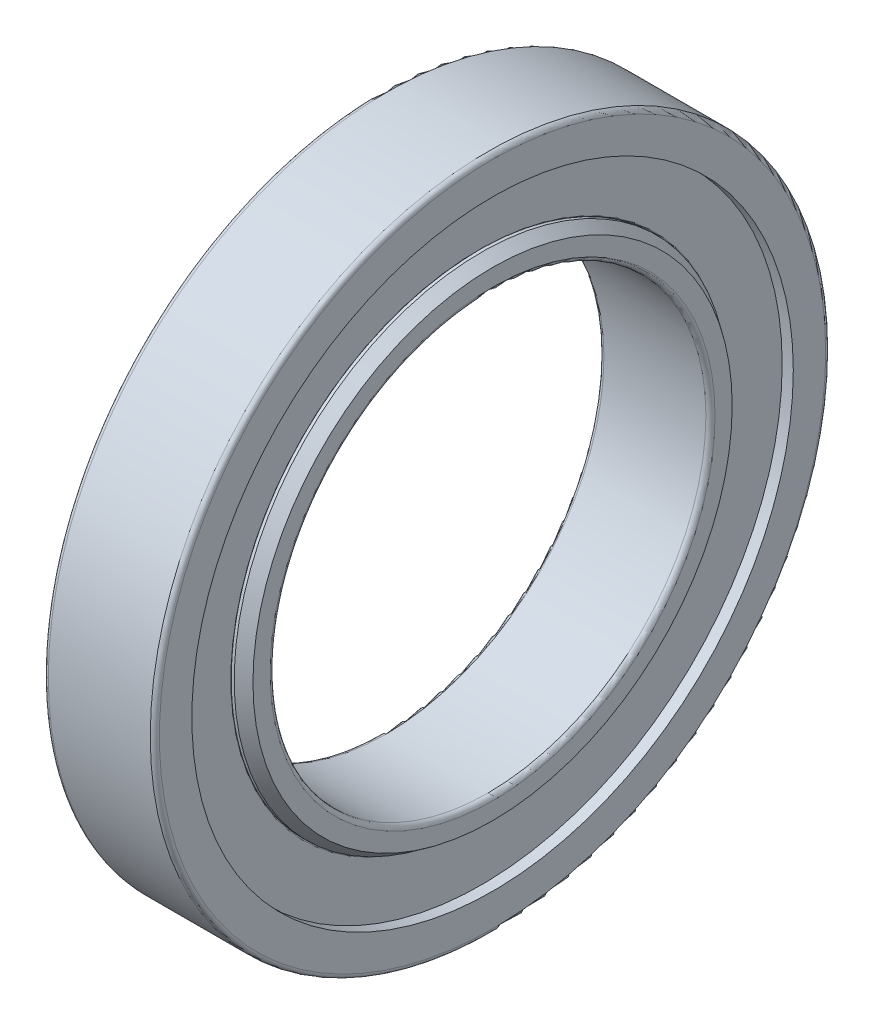
SolidWorks part; units mm, degrees
ref_plane "Plane1" through (0, 0, 0) normal (0, 0, 1) x (1, 0, 0)
ref_plane "Plane2" through (0, 0, 0) normal (0, 1, 0) x (1, 0, 0)
ref_plane "Plane3" through (0, 0, 0) normal (1, 0, 0) x (0, 0, -1)
sketch "Clipboard" plane through (0, 0, 0) normal (0, 0, 1) x (1, 0, 0)
  line L0 (-10, 0) -> (10, 0) construction
  line L1 (0, 0) -> (226.8117, -7.9204)
  line L2 (0, 0) -> (127.4223, 4.4497)
  line L3 (0, 0) -> (282.8776, -9.8783)
  line L4 (0, 0) -> (-22.3573, -0.3902)
  dimension "Race_OD" = 283.05
  dimension "Race_ID" = 226.95
sketch "OutRacSke" plane through (0, 0, 0) normal (0, 0, 1) x (1, 0, 0)
  line L0 (-20.4, 138.0188) -> (-25.5, 138.0188)
  line L1 (-25.5, 138.0188) -> (-25.5, 152.9)
  line L2 (-23.4, 155) -> (23.4, 155)
  line L3 (25.5, 152.9) -> (25.5, 138.0188)
  line L4 (25.5, 138.0188) -> (20.4, 138.0188)
  line L5 (20.4, 138.0188) -> (20.4, 141.525)
  line L6 (20.4, 141.525) -> (-20.4, 141.525)
  line L7 (-20.4, 141.525) -> (-20.4, 138.0188)
  line L8 (-90, 0) -> (90, 0) construction
  arc A0 (-25.5, 152.9) -> (-23.4, 155) centre (-23.4, 152.9) cw
  arc A1 (23.4, 155) -> (25.5, 152.9) centre (23.4, 152.9) cw
  dimension "Race_OD" = 283.05
  dimension "radius" = 2.1
  dimension "Width" = 51
  dimension "halfWidth" = 25.5
  dimension "groove_dp" = 3.5063
  dimension "Cyl_Len" = 40.8
revolve "OuterRace" add sketch "OutRacSke" angle 360 about L8 reverse direction yes
sketch "RolDetSke" plane through (0, 0, 0) normal (0, 0, 1) x (1, 0, 0)
  line L0 (-19.38, 140.9688) -> (-19.38, 127.5)
  line L1 (-19.38, 127.5) -> (19.38, 127.5)
  line L2 (19.38, 127.5) -> (19.38, 140.9688)
  line L3 (18.8188, 141.53) -> (-18.8188, 141.53)
  line L4 (-33.6, 127.5) -> (33.6, 127.5) construction
  arc A0 (19.38, 140.9688) -> (18.8188, 141.53) centre (18.8188, 140.9688) ccw
  arc A1 (-18.8188, 141.53) -> (-19.38, 140.9688) centre (-18.8188, 140.9688) ccw
  dimension "radius" = 0.5612
  dimension "Roller_diameter" = 28.06
  dimension "halfLength" = 19.38
revolve "RollerDetailed" [suppressed] add sketch "RolDetSke" angle 360 about L4 reverse direction yes
ref_axis "Axis1" through (-50, 0, 0) along (1, 0, 0)
sketch "RolSimSke" plane through (0, 101.6, 0) normal (0, 0, 1) x (1, 0, 0)
  line L0 (-19.38, 39.3688) -> (-19.38, 12.4312)
  line L1 (25.4, -101.6) -> (-25.4, -101.6) construction
  line L2 (19.38, 12.4312) -> (19.38, 39.3688)
  line L3 (18.8188, 39.93) -> (-18.8188, 39.93)
  line L5 (18.8188, 11.87) -> (-18.8188, 11.87)
  arc A0 (19.38, 39.3688) -> (18.8188, 39.93) centre (18.8188, 39.3688) ccw
  arc A1 (-18.8188, 39.93) -> (-19.38, 39.3688) centre (-18.8188, 39.3688) ccw
  arc A2 (19.38, 12.4312) -> (18.8188, 11.87) centre (18.8188, 12.4312) cw
  arc A3 (-18.8188, 11.87) -> (-19.38, 12.4312) centre (-18.8188, 12.4312) cw
  dimension "radius" = 0.5612
  dimension "D1" = 113.47
  dimension "Roller_diameter" = 28.06
  dimension "halfLength" = 19.38
revolve "RollersSimplified" add sketch "RolSimSke" angle 360 about L1
sketch "InsRacSke" plane through (0, 0, 0) normal (0, 0, 1) x (1, 0, 0)
  line L0 (-20.4, 113.475) -> (-25.5, 109.9688)
  line L1 (-25.5, 109.9688) -> (-25.5, 102.1)
  line L2 (-23.4, 100) -> (23.4, 100)
  line L3 (25.5, 102.1) -> (25.5, 109.9687)
  line L4 (25.5, 109.9687) -> (20.4, 113.475)
  line L5 (20.4, 113.475) -> (-20.4, 113.475)
  line L6 (-90, 0) -> (90, 0) construction
  line L7 (0, 0) -> (0, 177.8) construction
  arc A0 (-25.5, 102.1) -> (-23.4, 100) centre (-23.4, 102.1) ccw
  arc A1 (23.4, 100) -> (25.5, 102.1) centre (23.4, 102.1) ccw
  dimension "radius" = 2.1
  dimension "Race_ID" = 226.95
  dimension "Width" = 51
  dimension "halfWidth" = 25.5
  dimension "groove_dp" = 3.5063
  dimension "Cyl_Len" = 40.8
revolve "InnerRace" add sketch "InsRacSke" angle 360 about L6 reverse direction yes
pattern_circular "RollersDetailed" [suppressed] count 2 every 180 about axis through (-50, 0, 0) along (1, 0, 0)
sketch "CagSpiSke" plane through (0, 0, 0) normal (0, 0, 1) x (1, 0, 0)
  line L0 (22.95, 123.9925) -> (22.95, 131.0075)
  line L1 (22.95, 131.0075) -> (-22.95, 131.0075)
  line L2 (-22.95, 131.0075) -> (-22.95, 123.9925)
  line L3 (-22.95, 123.9925) -> (22.95, 123.9925)
  line L4 (-90, 0) -> (90, 0) construction
revolve "CageSpine" [suppressed] add sketch "CagSpiSke" angle 0.001 about L4
equation "\"CLdia@Clipboard\" =  ( \"Race_OD@Clipboard\" + \"Race_ID@Clipboard\" )  / 4"
equation "\"Race_OD@OutRacSke\" = \"Race_OD@Clipboard\""
equation "\"halfCylLen@OutRacSke\" = \"Cyl_Len@OutRacSke\" / 2"
equation "\"RolCLRad@RolDetSke\" = \"CLdia@Clipboard\""
equation "\"Roller_diameter@RolDetSke\" =  ( \"Race_OD@Clipboard\" - \"Race_ID@Clipboard\" )  / 2 + .01"
equation "\"Roller_diameter@RolSimSke\" =  ( \"Race_OD@Clipboard\" - \"Race_ID@Clipboard\" )  / 2 + .01"
equation "\"radius@RolDetSke\" = \"Roller_diameter@RolDetSke\" / 50"
equation "\"Length@RolDetSke\" = \"Cyl_Len@OutRacSke\" * .95"
equation "\"halfLength@RolDetSke\" = \"Length@RolDetSke\" / 2"
equation "\"thickness@CagSpiSke\"  = \"Roller_diameter@RolDetSke\" * .25"
equation "\"Cag_IR@CagSpiSke\" =  \"RolCLRad@RolDetSke\" * 2 - \"thickness@CagSpiSke\""
equation "\"Rol_Length@RolSimSke\" = \"Cyl_Len@InsRacSke\" * .95"
equation "\"halfLength@RolSimSke\" = \"Rol_Length@RolSimSke\" / 2"
equation "\"radius@RolSimSke\" = \"radius@RolDetSke\""
equation "\"D1@RolSimSke\" = \"CLdia@Clipboard\" -  ( \"Roller_diameter@RolSimSke\" / 2 ) "
equation "\"Max_count@Clipboard\" = int( 3.14159265 / atn(( \"Roller_diameter@RolDetSke\" / 2) / sqr( \"RolCLRad@RolDetSke\"  *  \"RolCLRad@RolDetSke\" - ( \"Roller_diameter@RolDetSke\" / 2) *  ( \"Roller_diameter@RolDetSke\" / 2))))"
equation "\"Max_count@Clipboard\" = ((sgn( \"Max_count@Clipboard\" - \"Count@Clipboard\" )-1)*( \"Max_count@Clipboard\" - \"Count@Clipboard\" ))/-2+ \"Count@Clipboard\""
equation "\"Count@RollersDetailed\" = int( \"Show_count@Clipboard\" ) "
equation "\"Count@RollersDetailed\" = ((sgn( \"Count@RollersDetailed\" - \"Max_count@Clipboard\" )-1)*( \"Count@RollersDetailed\" - \"Max_count@Clipboard\" ))/-2+ \"Max_count@Clipboard\""
equation "\"Count@RollersDetailed\" = ((sgn( \"Count@RollersDetailed\" - \"Min_count@Clipboard\" )+1)*( \"Count@RollersDetailed\" - \"Min_count@Clipboard\"))/2 +\"Min_count@Clipboard\""
equation "\"Angle@RollersDetailed\" = 360.0 / \"Max_count@Clipboard\""
equation "\"radius@InsRacSke\" = \"radius@OutRacSke\""
equation "\"groove_dp@InsRacSke\" = \"groove_dp@OutRacSke\""
equation "\"Width@InsRacSke\" = \"Width@OutRacSke\""
equation "\"halfWidth@OutRacSke\" = \"Width@OutRacSke\" / 2"
equation "\"halfWidth@InsRacSke\" = \"Width@InsRacSke\" / 2"
equation "\"Race_ID@InsRacSke\" = \"Race_ID@Clipboard\""
equation "\"Cyl_Len@InsRacSke\" = \"Cyl_Len@OutRacSke\""
equation "\"Angle@CageSpine\" =  \"Angle@RollersDetailed\" * ( \"Count@RollersDetailed\" -1 + int( \"Count@RollersDetailed\" / \"Max_count@Clipboard\" ) )  + 0.001 -  int( \"Count@RollersDetailed\" / \"Max_count@Clipboard\" ) * 0.001"
equation "\"Angle@CageSpine\" =  \"Angle@CageSpine\" * int( \"Min_count@Clipboard\" / 2) + int(1 / \"Min_count@Clipboard\")  * 0.001"
equation "\"width@CagSpiSke\" =   ( \"Width@InsRacSke\" + \"Cyl_Len@InsRacSke\" )  / 2"
equation "\"halfwidth@CagSpiSke\" = \"width@CagSpiSke\" / 2"
